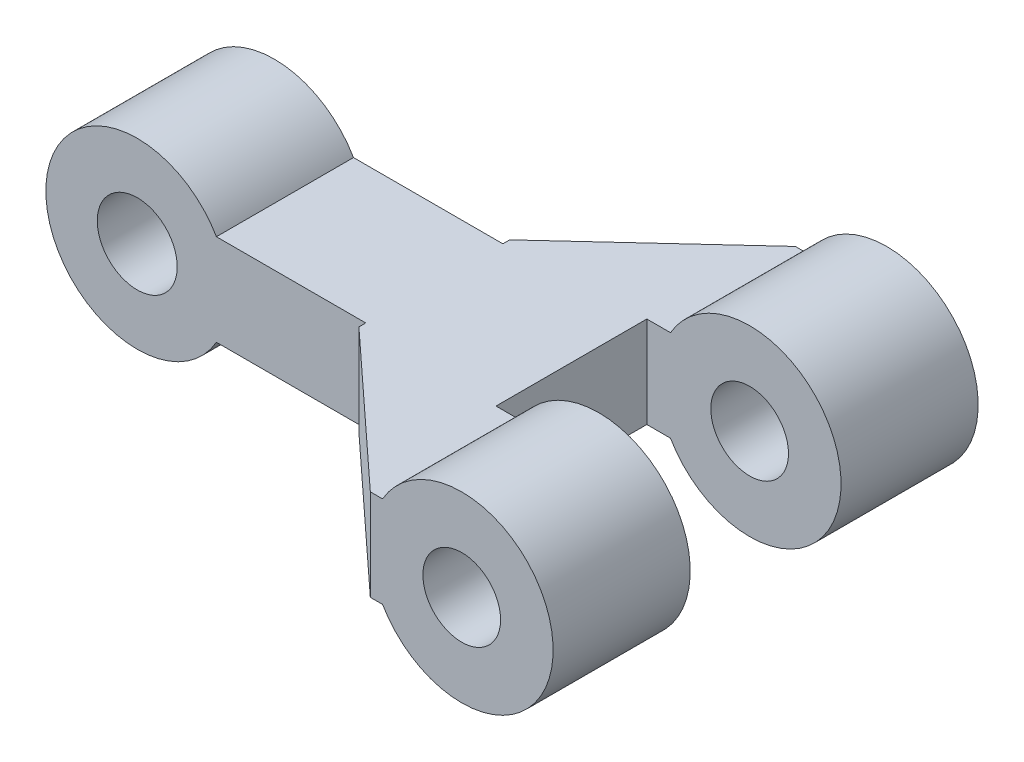
SolidWorks part; units mm, degrees
ref_plane "Спереди" through (0, 0, 0) normal (0, 0, 1) x (1, 0, 0)
ref_plane "Сверху" through (0, 0, 0) normal (0, 1, 0) x (1, 0, 0)
ref_plane "Справа" through (0, 0, 0) normal (1, 0, 0) x (0, 0, -1)
other "Configuration Table"
sketch "Эскиз1" plane through (0, 0, 0) normal (0, 0, 1) x (1, 0, 0)
  circle A0 centre (0, 0) radius 1.7
  circle A1 centre (0, 0) radius 4
  dimension "D1" = 3.4
  dimension "D2" = 8
extrude "Бобышка-Вытянуть1" add sketch "Эскиз1" along normal blind 6
sketch "Эскиз2" plane through (0, 0, 0) normal (0, 1, 0) x (1, 0, 0)
  line L0 (-4, 0) -> (-10.5, -6)
  line L1 (-10.5, -6) -> (-10.5, -12.6)
  line L2 (-10.5, -12.6) -> (-4, -18.6)
  line L4 (-4, -12.6) -> (-4.5, -12.6)
  line L5 (-4.5, -12.6) -> (-4.5, -6)
  line L6 (-4.5, -6) -> (-4, -6)
  line L7 (-4, 0) -> (-4, -6) construction
  line L9 (2.5677, -9.3) -> (-17.3387, -9.3) construction
  line L10 (-4, -6) -> (4, -6) construction
  line L11 (-4, 0) -> (-3, 0)
  line L12 (-3, 0) -> (-3, -6)
  line L13 (-3, -6) -> (-4, -6)
  line L14 (-4, -12.6) -> (-3, -12.6)
  line L15 (-3, -12.6) -> (-3, -18.6)
  line L16 (-3, -18.6) -> (-4, -18.6)
  dimension "D1" = 3.3
  dimension "D2" = 6
  dimension "D3" = 0.5
  dimension "D4" = 6
  dimension "D5" = 1
  dimension "D6" = 1
extrude "Бобышка-Вытянуть2" add sketch "Эскиз2" along normal blind 2 and the other way blind 2
ref_plane "Плоскость1" through (0, 0, 9.3) normal (0, 0, -1) x (-1, 0, 0)
mirror "Зеркальное отражение1" about plane through (0, 0, 9.3) normal (0, 0, -1) of "Бобышка-Вытянуть1"
sketch "Эскиз3" plane through (0, 0, 9.3) normal (0, 0, -1) x (-1, 0, 0)
  line L10 (1.741, 0) -> (46.1169, 0) construction
  line L12 (10.5, 2) -> (17.0359, 2)
  line L14 (10.5, -2) -> (17.0359, -2)
  line L15 (10.5, 2) -> (10.5, -2)
  circle A9 centre (20.5, 0) radius 1.75
  arc A10 (17.0359, -2) -> (17.0359, 2) centre (20.5, 0) ccw
  dimension "D2" = 8
  dimension "D3" = 10
  dimension "D1" = 3.5
extrude "Бобышка-Вытянуть3" add sketch "Эскиз3" along normal blind 3 and the other way blind 3
